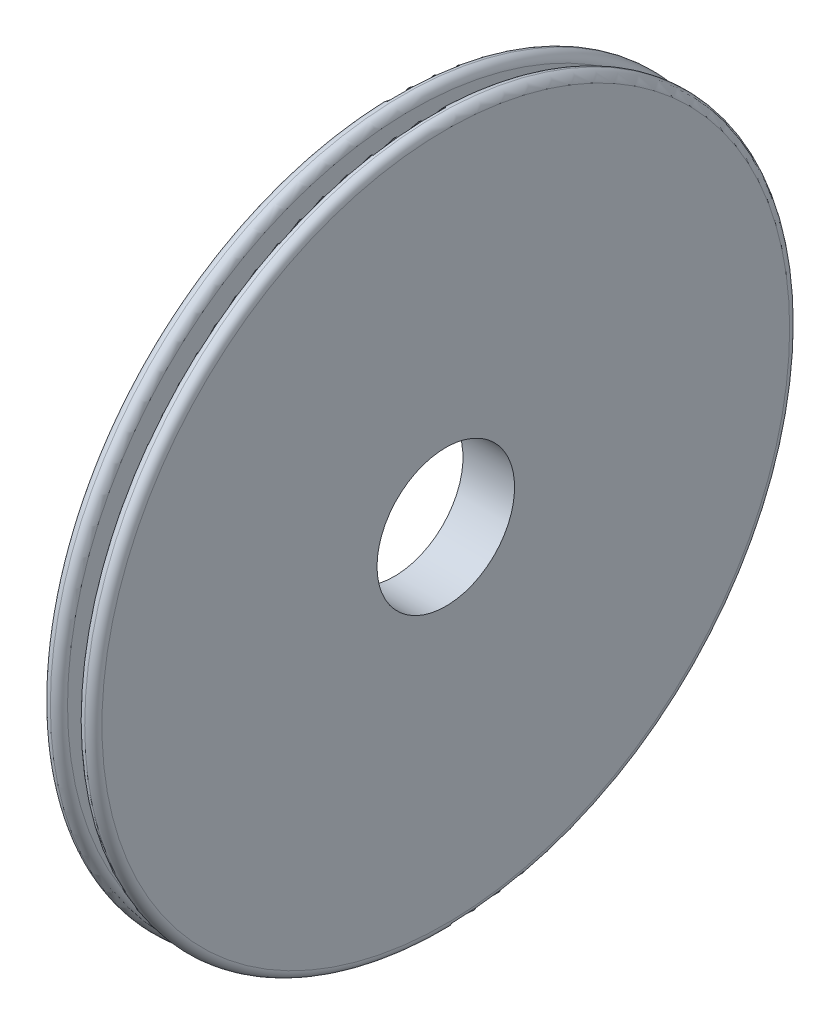
SolidWorks part; units mm, degrees
ref_plane "Plan de face" through (0, 0, 0) normal (0, 0, 1) x (1, 0, 0)
ref_plane "Plan de dessus" through (0, 0, 0) normal (0, 1, 0) x (1, 0, 0)
ref_plane "Plan de droite" through (0, 0, 0) normal (1, 0, 0) x (0, 0, -1)
sketch "Esquisse1" plane through (0, 0, 0) normal (0, 0, 1) x (1, 0, 0)
  line L0 (-1, 36) -> (1, 36)
  line L1 (1, 36) -> (1, 41)
  line L2 (1, 41) -> (3, 41)
  line L3 (3, 41) -> (3, 8)
  line L4 (0, 8) -> (0, 4.5601) construction
  line L5 (-3, 41) -> (-3, 8)
  line L6 (-1, 41) -> (-3, 41)
  line L7 (-1, 36) -> (-1, 41)
  line L9 (-3, 8) -> (3, 8)
  line L10 (0, 0) -> (11.3771, 0)
  point P12 (0, 36)
  dimension "D1" = 1
  dimension "D2" = 2
  dimension "D3" = 5
  dimension "D4" = 36
  dimension "D5" = 8
revolve "Révolution2" add sketch "Esquisse1" angle 360 about L10
fillet "Congé1" radius 1 4 edges at (-3, 0, 41) (-1, 0, 41) (3, 0, 41) (1, 0, 41)
